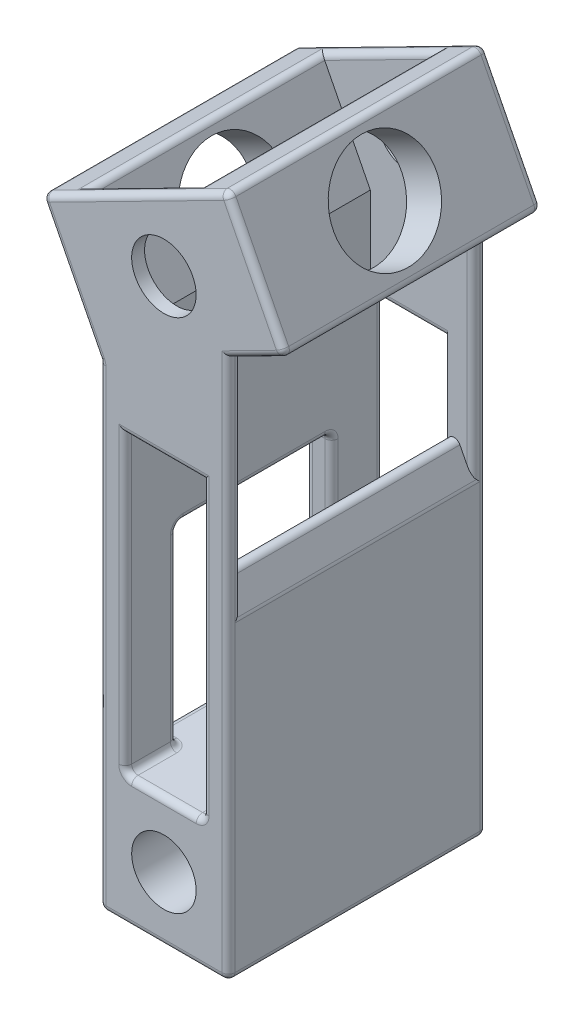
SolidWorks part; units mm, degrees
ref_plane "Front Plane" through (0, 0, 0) normal (0, 0, 1) x (1, 0, 0)
ref_plane "Top Plane" through (0, 0, 0) normal (0, 1, 0) x (1, 0, 0)
ref_plane "Right Plane" through (0, 0, 0) normal (1, 0, 0) x (0, 0, -1)
sketch "Sketch1" plane through (0, 0, 0) normal (0, 0, 1) x (1, 0, 0)
  line L2 (-3.2879, 12.4524) -> (-3.2879, -24.3884)
  line L3 (-3.2879, -24.3884) -> (6.7121, -24.3884)
  line L12 (6.7121, 17.5476) -> (6.7121, -24.3884)
  line L17 (1.7121, -24.3884) -> (1.7121, 20.6116) construction
  line L18 (1.7121, 20.6116) -> (37.3523, 38.7713) construction
  line L20 (6.5702, 28.6986) -> (11.1101, 19.7885)
  line L21 (11.1101, 19.7885) -> (6.7121, 17.5476)
  line L22 (6.5702, 28.6986) -> (-7.8278, 21.3624)
  line L26 (6.7121, 17.5476) -> (-3.2879, 12.4524) construction
  line L27 (-3.2879, 12.4524) -> (-7.8278, 21.3624)
  circle A0 centre (1.7121, 20.6116) radius 2.5 construction
  point P0 (0, 0)
  point P9 (0, 0)
  dimension "D6" = 5
  dimension "D7" = 10
  dimension "D1" = 10
  dimension "D3" = 117
  dimension "D4" = 117
  dimension "D5" = 45
  dimension "D8" = 40
  dimension "D9" = 5
  dimension "D10" = 8
extrude "Boss-Extrude1" add sketch "Sketch1" along normal blind 20
sketch "Sketch2" plane through (0, 0, 0) normal (0, 0, -1) x (-1, 0, 0)
  line L0 (-1.7121, -24.3884) -> (-1.7121, 23.685) construction
  line L1 (3.2879, -24.3884) -> (-6.7121, -24.3884) construction
  circle A0 centre (-1.7121, -19.3884) radius 2.5
  circle A1 centre (-1.7121, 20.6116) radius 2.5
  dimension "D1" = 5
  dimension "D3" = 5
  dimension "D2" = 5
  dimension "D4" = 45
extrude "Cut-Extrude1" cut sketch "Sketch2" against normal up to next
sketch "Sketch5" plane through (-10.2547, 20.1259, 0) normal (-0.454, 0.891, 0) x (0.891, 0.454, 0)
  line L0 (18.8829, 0) -> (10.8829, 0) construction
  line L1 (18.8829, 0) -> (2.7237, 0) construction
  line L2 (10.8829, 0) -> (10.8033, -20) construction
  line L3 (18.8829, -20) -> (2.7237, -20) construction
  line L5 (15.8431, -1) -> (5.8431, -1)
  line L6 (15.8431, -1) -> (15.8431, -19)
  line L7 (15.8431, -19) -> (5.8431, -19)
  line L8 (5.8431, -1) -> (5.8431, -19)
  line L9 (15.8431, -1) -> (5.8431, -19) construction
  line L10 (15.8431, -19) -> (5.8431, -1) construction
  point P5 (10.8431, -10)
  dimension "D1" = 8
  dimension "D2" = 10
  dimension "D3" = 18
extrude "Cut-Extrude4" cut sketch "Sketch5" against normal through all
sketch "Sketch6" plane through (16.8248, 8.5727, 0) normal (0.891, 0.454, 0) x (0, 0, -1)
  line L0 (0, 17.5878) -> (-20, 17.5878) construction
  line L1 (0, 12.5878) -> (0, 22.5878) construction
  line L2 (-20, 12.5878) -> (-20, 22.5878) construction
  circle A0 centre (-10, 17.5878) radius 4
  dimension "D1" = 8
extrude "Cut-Extrude5" cut sketch "Sketch6" against normal through all
sketch "Sketch8" plane through (0, 0, 20) normal (0, 0, 1) x (1, 0, 0)
  line L0 (1.7121, -19.3884) -> (1.7121, -14.3884) construction
  line L1 (-3.2879, 12.4524) -> (6.7121, 12.4524) construction
  line L2 (6.7121, -24.3884) -> (6.7121, 17.5476) construction
  line L3 (1.7121, 12.4524) -> (1.7121, 8.4524) construction
  line L4 (1.7121, 8.4524) -> (1.7121, -14.3884) construction
  line L6 (-1.2879, -14.3884) -> (4.7121, -14.3884)
  line L7 (-1.2879, -14.3884) -> (-1.2879, 8.4524)
  line L8 (-1.2879, 8.4524) -> (4.7121, 8.4524)
  line L9 (4.7121, -14.3884) -> (4.7121, 8.4524)
  line L10 (-1.2879, -14.3884) -> (4.7121, 8.4524) construction
  line L11 (-1.2879, 8.4524) -> (4.7121, -14.3884) construction
  point P10 (1.7121, -2.968)
  dimension "D1" = 5
  dimension "D2" = 4
  dimension "D3" = 6
extrude "Cut-Extrude6" cut sketch "Sketch8" against normal through all
sketch "Sketch12" plane through (0, 8.4524, 0) normal (0, -1, 0) x (1, 0, 0)
  line L0 (-1.2879, 10) -> (2.2512, 10) construction
  line L3 (-1.2879, 0) -> (-1.2879, 20) construction
  line L4 (2.2512, 19) -> (2.2512, 1) construction
  line L6 (-1.2879, 1) -> (2.2512, 1)
  line L7 (-1.2879, 1) -> (-1.2879, 19)
  line L8 (-1.2879, 19) -> (2.2512, 19)
  line L9 (2.2512, 1) -> (2.2512, 19)
  line L10 (-1.2879, 1) -> (2.2512, 19) construction
  line L11 (-1.2879, 19) -> (2.2512, 1) construction
  point P7 (0.4816, 10)
extrude "Cut-Extrude7" cut sketch "Sketch12" against normal through all
sketch "Sketch13" plane through (-3.2879, 0, 0) normal (-1, 0, 0) x (0, 0, 1)
  line L0 (10, 12.4524) -> (10, 0.4524) construction
  line L2 (20, -24.3884) -> (0, -24.3884) construction
  line L3 (20, -14.3884) -> (0, -14.3884) construction
  line L4 (20, 12.4524) -> (20, -24.3884) construction
  line L5 (0, 12.4524) -> (0, -24.3884) construction
  line L6 (20, 12.4524) -> (0, 12.4524) construction
  line L7 (10, 0.4524) -> (10, -14.3884) construction
  line L9 (16, 0.4524) -> (4, 0.4524)
  line L10 (16, 0.4524) -> (16, -14.3884)
  line L11 (16, -14.3884) -> (4, -14.3884)
  line L12 (4, 0.4524) -> (4, -14.3884)
  line L13 (16, 0.4524) -> (4, -14.3884) construction
  line L14 (16, -14.3884) -> (4, 0.4524) construction
  point P12 (10, -6.968)
  dimension "D1" = 10
  dimension "D2" = 12
  dimension "D3" = 12
extrude "Cut-Extrude8" cut sketch "Sketch13" against normal up to next
fillet "Fillet2" radius 0.5 56 edges at (-2.2879, -14.3884, 4) (-1.2879, -14.3884, 18) (-1.2879, -14.3884, 2) (4.7121, -14.3884, 10) (-1.2879, -6.968, 4) (-2.2879, 0.4524, 4) (-1.2879, 0.4524, 10) (-2.2879, 0.4524, 16) (-2.2879, -14.3884, 16) (-1.2879, -6.968, 16) (1.7121, 8.4524, 19) (1.7121, 8.4524, 0) (1.7121, 8.4524, 1) (4.7121, -2.968, 0) (-1.2879, -2.968, 0) (1.7121, -14.3884, 0) (1.7121, 8.4524, 20) (4.7121, -2.968, 20) (1.7121, -14.3884, 20) (-1.2879, -2.968, 20) (-3.2879, -14.3884, 10) (-3.2879, -6.968, 4) (-3.2879, 0.4524, 10) (-3.2879, -6.968, 16) (1.7121, -24.3884, 20) (1.7121, -24.3884, 0) (-3.2879, -24.3884, 10) (-3.2879, -5.968, 20) (-5.5579, 16.9074, 20) (-3.2879, 12.4524, 10) (-5.5579, 16.9074, 0) (-3.2879, -5.968, 0) (-0.6288, 25.0305, 20) (-0.5934, 25.0486, 19) (-5.0484, 22.7786, 10) (-7.8278, 21.3624, 10) (-0.6288, 25.0305, 0) (-0.5934, 25.0486, 1) (3.8617, 27.3185, 10) (6.5702, 28.6986, 10) (8.8401, 24.2436, 20) (8.8401, 24.2436, 0) (11.1101, 19.7885, 10) (7.5568, 17.9781, 19) (8.9111, 18.6681, 20) (7.5568, 17.9781, 1) (8.4016, 18.4085, 10) (6.7121, 8.6225, 1) (4.7121, 6.0375, 19) (6.7121, 8.6225, 19) (4.7121, 3.6227, 10) (6.7121, -0.3026, 10) (8.9111, 18.6681, 0) (6.7121, -3.4204, 0) (6.7121, -24.3884, 10) (6.7121, -3.4204, 20)
